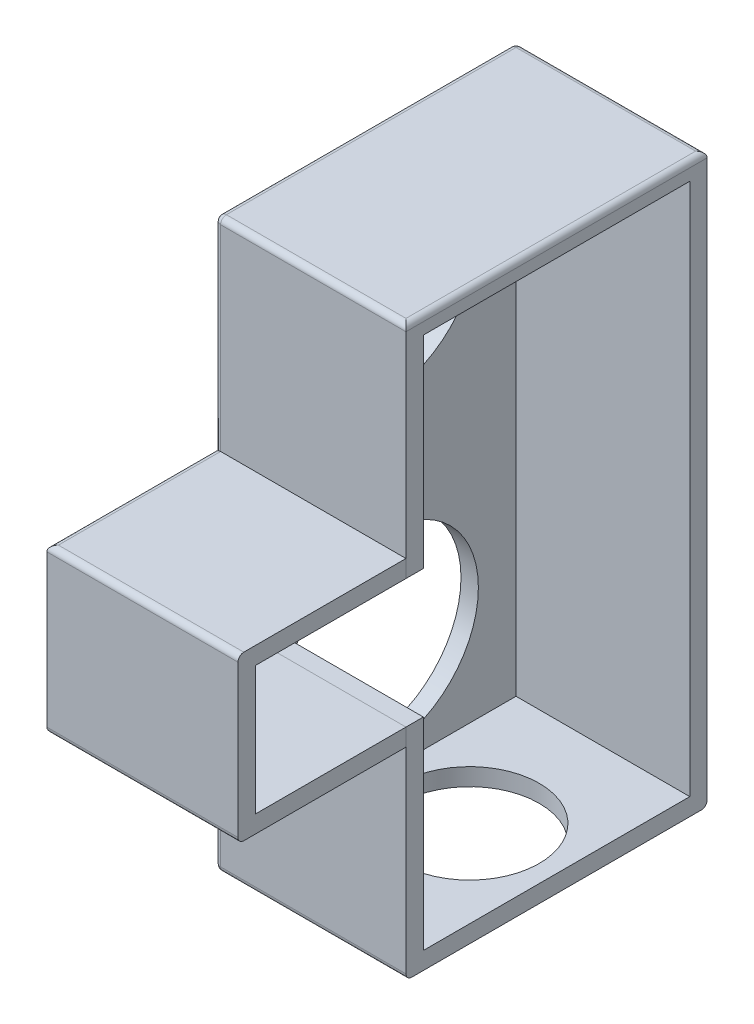
SolidWorks part; units mm, degrees
ref_plane "前视基准面" through (0, 0, 0) normal (0, 0, 1) x (1, 0, 0)
ref_plane "上视基准面" through (0, 0, 0) normal (0, 1, 0) x (1, 0, 0)
ref_plane "右视基准面" through (0, 0, 0) normal (1, 0, 0) x (0, 0, -1)
other "Configuration Table"
sketch "草图1" plane through (0, 0, 0) normal (0, 1, 0) x (1, 0, 0)
  line L1 (7.5, -11.5) -> (-7.5, -11.5)
  line L2 (7.5, -11.5) -> (7.5, 11.5)
  line L3 (7.5, 11.5) -> (-7.5, 11.5)
  line L4 (-7.5, -11.5) -> (-7.5, 11.5)
  line L5 (7.5, -11.5) -> (-7.5, 11.5) construction
  line L6 (7.5, 11.5) -> (-7.5, -11.5) construction
  point P0 (0, 0)
  dimension "D1" = 23
  dimension "D2" = 15
extrude "凸台-拉伸1" add sketch "草图1" along normal blind 46
ref_plane "基准面1" through (0, 0, 0) normal (0, -1, 0) x (-1, 0, 0)
sketch "草图2" plane through (0, 0, 0) normal (0, -1, 0) x (-1, 0, 0)
  circle A0 centre (0, 0) radius 6
shell "抽壳1" thickness 1.5 removed face at (7.5, 23, 0) outward yes
extrude "切除-拉伸4" cut sketch "草图2" along normal blind 1.5
ref_plane "基准面2" through (-9, 0, 0) normal (-1, 0, 0) x (0, 0, 1)
sketch "草图3" plane through (-9, 0, 0) normal (-1, 0, 0) x (0, 0, 1)
  line L0 (13, 23) -> (-13, 23) construction
  line L1 (13, 47.5) -> (13, -1.5) construction
  line L2 (-13, 47.5) -> (-13, -1.5) construction
  line L3 (0, 47.5) -> (0, -1.5) construction
  line L4 (-13, 47.5) -> (13, 47.5) construction
  line L5 (-13, -1.5) -> (13, -1.5) construction
  line L6 (5.2537, 28) -> (-4.4001, 28) construction
  line L7 (5.2537, 18) -> (-3.777, 18) construction
  circle A0 centre (0, 36.25) radius 8.25
  circle A1 centre (0, 9.75) radius 8.25
  dimension "D3" = 16.5
  dimension "D1" = 5
  dimension "D2" = 5
extrude "切除-拉伸5" cut sketch "草图3" against normal blind 1.5
ref_plane "基准面3" through (0, 0, 11.5) normal (0, 0, -1) x (-1, 0, 0)
sketch "草图4" plane through (0, 0, 11.5) normal (0, 0, -1) x (-1, 0, 0)
  line L0 (7.5, 46) -> (7.5, 0) construction
  line L1 (7.5, 46) -> (7.5, 0) construction
  line L2 (7.5, 28.55) -> (7.5, 17.45)
  line L3 (7.5, 28.55) -> (-6, 28.55)
  line L4 (-6, 28.55) -> (-6, 17.45)
  line L5 (-6, 17.45) -> (7.5, 17.45)
  line L6 (-7.5, 46) -> (-7.5, 0) construction
  line L7 (-7.5, 46) -> (-7.5, 0) construction
  line L8 (-6, 28.55) -> (-7.5, 28.55) construction
  line L9 (-7.5, 28.55) -> (-7.5, 17.45) construction
  line L10 (-7.5, 17.45) -> (-6, 17.45) construction
  point P5 (7.5, 23)
  dimension "D1" = 11.1
  dimension "D2" = 1.5
extrude "切除-拉伸6" cut sketch "草图4" against normal blind 10
ref_plane "基准面4" through (0, 0, 13) normal (0, 0, 1) x (1, 0, 0)
sketch "草图5" plane through (0, 0, 13) normal (0, 0, 1) x (1, 0, 0)
  line L0 (-7.5, 28.55) -> (6, 28.55) construction
  line L1 (-7.5, 17.45) -> (-7.5, 28.55) construction
  line L2 (-9, 47.5) -> (-9, -1.5) construction
  line L3 (-7.5, 28.55) -> (6, 28.55)
  line L4 (-7.5, 17.45) -> (-7.5, 28.55)
  line L5 (-9, 47.5) -> (-9, -1.5) construction
  line L6 (6, 17.45) -> (-7.5, 17.45) construction
  line L7 (6, 28.55) -> (6, 17.45) construction
  line L8 (6, 17.45) -> (-7.5, 17.45)
  line L9 (6, 28.55) -> (6, 17.45) construction
  line L10 (7.5, 17.45) -> (7.5, 28.55) construction
  line L11 (7.5, 47.5) -> (7.5, -1.5) construction
  line L12 (6, 17.45) -> (7.5, 17.45)
  line L13 (7.5, 17.45) -> (7.5, 28.55)
  line L14 (7.5, 28.55) -> (6, 28.55)
  dimension "D1" = 11.1
extrude "凸台-拉伸2" add sketch "草图5" along normal blind 13 separate body
shell "抽壳2" thickness 1.5 removed face at (0, 23, 13) removed face at (7.5, 23, 19.5) outward yes
ref_plane "基准面5" through (-9, 0, 0) normal (-1, 0, 0) x (0, 0, 1)
sketch "草图6" plane through (-9, 0, 0) normal (-1, 0, 0) x (0, 0, 1)
  line L0 (27.5, 15.95) -> (13, 15.95) construction
  line L1 (27.5, 30.05) -> (27.5, 15.95) construction
  line L2 (13, 30.05) -> (13, 15.95) construction
  line L3 (27.5, 30.05) -> (13, 30.05) construction
  line L4 (27.5, 15.95) -> (13, 15.95) construction
  line L5 (27.5, 30.05) -> (27.5, 15.95) construction
  line L6 (13, 30.05) -> (13, 15.95) construction
  line L7 (27.5, 30.05) -> (13, 30.05) construction
  line L8 (13, 23) -> (17.49, 21.6035)
  line L9 (27.5, 18.4901) -> (23.5661, 23.0331)
  line L10 (17.49, 30.05) -> (17.49, 24.4303)
  line L11 (17.49, 15.95) -> (21.3183, 20.4128)
  line L12 (27.5, 27.619) -> (21.3042, 25.6453)
  line L13 (21.3183, 20.4128) -> (27.5, 18.4901)
  line L14 (23.5661, 23.0331) -> (27.5, 27.619)
  line L15 (21.3042, 25.6453) -> (17.49, 30.05)
  line L16 (17.49, 24.4303) -> (13, 23)
  line L17 (17.49, 21.6035) -> (17.49, 15.95)
fillet "圆角3" radius 0.5 9 edges at (-0.75, 47.5, -13) (-0.75, -1.5, -13) (-9, 23, -13) (-9, 23, 13) (7.5, 47.5, 0) (-0.75, 47.5, 13) (-0.75, -1.5, 13) (-9, 47.5, 0) (-9, -1.5, 0)
ref_plane "基准面6" through (0, 0, 13) normal (0, 0, 1) x (1, 0, 0)
sketch "草图7" plane through (0, 0, 13) normal (0, 0, 1) x (1, 0, 0)
  line L0 (-7.5, 17.45) -> (7.5, 17.45) construction
  line L1 (7.5, 47) -> (7.5, -1) construction
  line L2 (6, 28.55) -> (6, 17.45) construction
  line L3 (7.5, 28.55) -> (-7.5, 28.55) construction
  line L4 (-7.5, 17.45) -> (7.5, 17.45) construction
  line L5 (7.5, 47) -> (7.5, -1) construction
  line L6 (6, 28.55) -> (6, 17.45) construction
  line L7 (7.5, 28.55) -> (-7.5, 28.55) construction
  line L8 (6, 28.55) -> (7.5, 28.55)
  line L9 (7.5, 28.55) -> (7.5, 17.45)
  line L10 (7.5, 17.45) -> (6, 17.45)
  line L11 (6, 17.45) -> (6, 28.55)
extrude "切除-拉伸7" cut sketch "草图7" against normal blind 1.5
fillet "圆角4" radius 0.5 4 edges at (-0.75, 15.95, 27.5) (-0.75, 30.05, 27.5) (-9, 15.95, 20.25) (-9, 30.05, 20.25)
